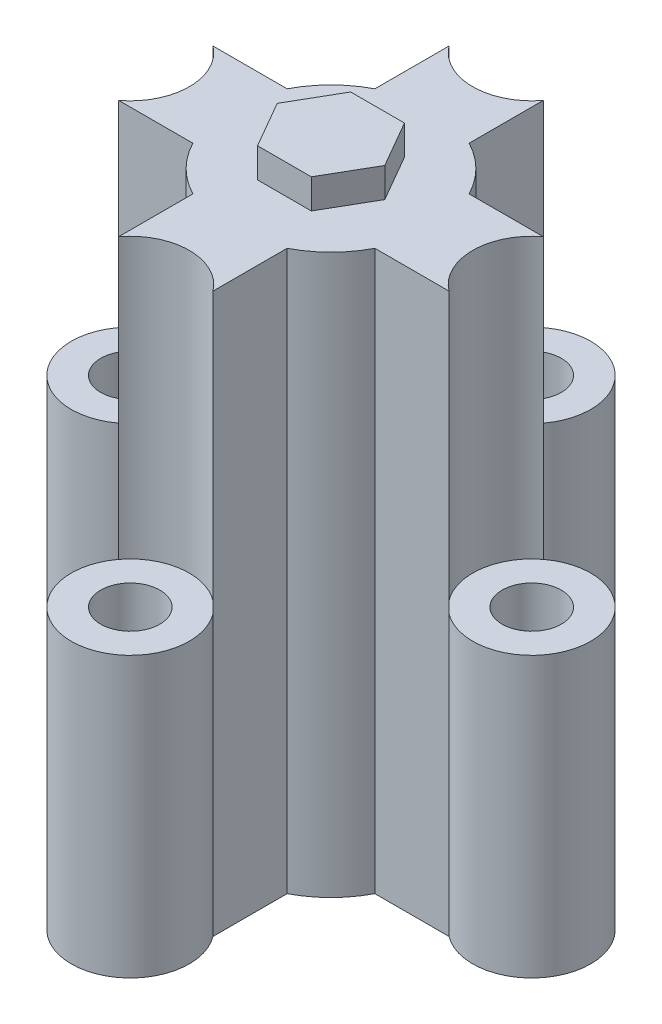
SolidWorks part; units mm, degrees
ref_plane "Front Plane" through (0, 0, 0) normal (0, 0, 1) x (1, 0, 0)
ref_plane "Top Plane" through (0, 0, 0) normal (0, 1, 0) x (1, 0, 0)
ref_plane "Right Plane" through (0, 0, 0) normal (1, 0, 0) x (0, 0, -1)
sketch "Sketch1" plane through (0, 0, 0) normal (0, 1, 0) x (1, 0, 0)
  line L1 (17.7275, 5.0583) -> (9.768, 5.0583)
  line L2 (17.7275, -5.0583) -> (9.768, -5.0583)
  line L3 (5.0583, -17.7275) -> (5.0583, -9.768)
  line L4 (-5.0583, -17.7275) -> (-5.0583, -9.768)
  line L5 (-17.7275, -5.0583) -> (-9.768, -5.0583)
  line L6 (-17.7275, 5.0583) -> (-9.768, 5.0583)
  line L7 (-5.0583, 17.7275) -> (-5.0583, 9.768)
  line L8 (5.0583, 17.7275) -> (5.0583, 9.768)
  circle A0 centre (0, 0) radius 11
  circle A3 centre (21.548, 0) radius 3.175
  circle A4 centre (21.548, 0) radius 6.339
  circle A6 centre (0, -21.548) radius 6.339
  circle A7 centre (0, -21.548) radius 3.175
  circle A8 centre (-21.548, 0) radius 6.339
  circle A9 centre (-21.548, 0) radius 3.175
  circle A10 centre (0, 21.548) radius 6.339
  circle A11 centre (0, 21.548) radius 3.175
  point P35 (0, 0)
  dimension "D1" = 21.548
  dimension "D2" = 12.678
  dimension "D3" = 6.35
  dimension "D5" = 22
  dimension "D6" = 4
extrude "Boss-Extrude1" add sketch "Sketch1" along normal blind 60 contours A10 L7 A0 L8 | A8 L5 A0 L6 | A0 | A4 L1 A0 L2 | A6 L3 A0 L4 region at (13.3193, 0, 0) region at (0, 0, 0) region at (0, 0, -13.3193) region at (0, 0, 13.3193) region at (-13.3193, 0, 0)
extrude "Boss-Extrude2" add sketch "Sketch1<3>" along normal blind 30 contours A8 A9 | A6 A7 | A4 A3 | A10 A11 region at (24.2934, 0, -5.5141) region at (0, 0, -15.3883) region at (5.8403, 0, 19.5902) region at (-16.0339, 0, -2.7454)
sketch "Sketch1<3>" plane through (0, 0, 0) normal (0, 1, 0) x (1, 0, 0) same geometry as "Sketch1"
sketch "Sketch2" plane through (0, 60, 0) normal (0, 1, 0) x (1, 0, 0)
  line L1 (5.7735, 0) -> (2.8868, 5)
  line L2 (2.8868, 5) -> (-2.8868, 5)
  line L3 (-2.8868, 5) -> (-5.7735, 0)
  line L4 (-5.7735, 0) -> (-2.8868, -5)
  line L5 (-2.8868, -5) -> (2.8868, -5)
  line L6 (2.8868, -5) -> (5.7735, 0)
  circle A0 centre (0, 0) radius 5 construction
extrude "Boss-Extrude3" add sketch "Sketch2" along normal blind 3.175
